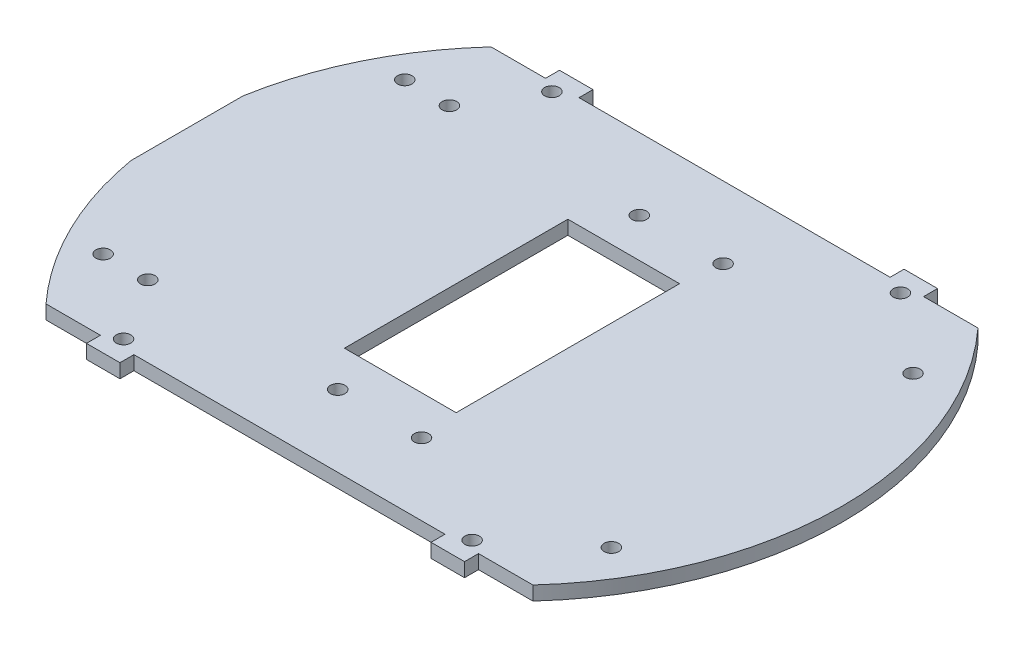
SolidWorks part; units mm, degrees
material "Acrylic (Medium-high impact)"
ref_plane "Front Plane" through (0, 0, 0) normal (0, 0, 1) x (1, 0, 0)
ref_plane "Top Plane" through (0, 0, 0) normal (0, 1, 0) x (1, 0, 0)
ref_plane "Right Plane" through (0, 0, 0) normal (1, 0, 0) x (0, 0, -1)
sketch "Sketch1" plane through (0, 0, 0) normal (0, 1, 0) x (1, 0, 0)
  line L0 (-73.9169, 12.7) -> (-73.9169, -12.7)
  line L1 (-35.3642, -50.6035) -> (-35.3642, -53.7785)
  line L2 (-55.356, -50.6035) -> (-42.9842, -50.6035)
  line L3 (-55.356, 50.6035) -> (-42.9842, 50.6035)
  line L4 (-48.5169, -34.29) -> (-48.5169, 34.29) construction
  line L5 (-48.5169, 34.29) -> (-5.3369, 34.29) construction
  line L6 (-5.3369, 34.29) -> (-5.3369, -34.29) construction
  line L7 (-5.3369, -34.29) -> (-48.5169, -34.29) construction
  line L8 (-73.9169, 0) -> (-48.5169, 0) construction
  line L9 (0, 50.6035) -> (0, -51.6195) construction
  line L10 (-73.9169, 12.7) -> (-73.9169, -12.7) construction
  line L11 (-12.7, 25.4) -> (12.7, 25.4)
  line L12 (-12.7, 25.4) -> (-12.7, -25.4)
  line L13 (-12.7, -25.4) -> (12.7, -25.4)
  line L14 (12.7, 25.4) -> (12.7, -25.4)
  line L15 (0, 0) -> (0, 25.4) construction
  line L16 (0, 0) -> (-12.7, 0) construction
  line L17 (13.7131, 34.29) -> (13.7131, -34.29) construction
  line L18 (13.7131, -34.29) -> (56.8931, -34.29) construction
  line L19 (56.8931, -34.29) -> (56.8931, 34.29) construction
  line L20 (56.8931, 34.29) -> (13.7131, 34.29) construction
  line L21 (39.6269, 48.6985) -> (39.6269, 50.6035) construction
  line L22 (39.6269, -48.6985) -> (39.6269, -50.6035) construction
  line L23 (-39.6269, -48.6985) -> (-39.6269, -50.6035) construction
  line L24 (-39.6269, 48.6985) -> (-39.6269, 50.6035) construction
  line L25 (39.6269, 48.6985) -> (41.2779, 48.6985) construction
  line L26 (39.6269, -48.6985) -> (41.2779, -48.6985) construction
  line L27 (-35.3642, -50.6035) -> (35.3642, -50.6035)
  line L28 (35.3642, -50.6035) -> (35.3642, -53.7785)
  line L29 (35.3642, -53.7785) -> (42.9842, -53.7785)
  line L30 (42.9842, -50.6035) -> (42.9842, -53.7785)
  line L31 (-35.3642, -53.7785) -> (-42.9842, -53.7785)
  line L32 (-42.9842, -50.6035) -> (-42.9842, -53.7785)
  line L33 (42.9842, 50.6035) -> (42.9842, 53.7785)
  line L34 (35.3642, 53.7785) -> (42.9842, 53.7785)
  line L35 (35.3642, 50.6035) -> (35.3642, 53.7785)
  line L36 (-35.3642, 50.6035) -> (-35.3642, 53.7785)
  line L37 (-35.3642, 53.7785) -> (-42.9842, 53.7785)
  line L38 (-42.9842, 50.6035) -> (-42.9842, 53.7785)
  line L39 (42.9842, -50.6035) -> (55.356, -50.6035)
  line L40 (42.9842, 50.6035) -> (55.356, 50.6035)
  line L41 (-35.3642, 50.6035) -> (35.3642, 50.6035)
  arc A0 (-73.9169, -12.7) -> (-55.356, -50.6035) centre (0, 0) ccw
  circle A1 centre (13.7131, 34.29) radius 1.651
  arc A2 (-55.356, 50.6035) -> (-73.9169, 12.7) centre (0, 0) ccw
  arc A3 (55.356, -50.6035) -> (55.356, 50.6035) centre (0, 0) ccw
  circle A4 centre (-58.6769, -34.29) radius 1.651
  circle A5 centre (-58.6769, 34.29) radius 1.651
  circle A6 centre (-39.6269, 48.6985) radius 1.651
  circle A7 centre (39.6269, 48.6985) radius 1.651
  circle A8 centre (-39.6269, -48.6985) radius 1.651
  circle A9 centre (39.6269, -48.6985) radius 1.651
  circle A10 centre (56.8931, 34.29) radius 1.651
  circle A11 centre (-58.6769, 34.29) radius 1.651 construction
  circle A12 centre (-48.5169, 34.29) radius 1.651
  circle A13 centre (-5.3369, 34.29) radius 1.651
  circle A14 centre (-5.3369, -34.29) radius 1.651
  circle A15 centre (-48.5169, -34.29) radius 1.651
  circle A16 centre (13.7131, -34.29) radius 1.651
  circle A17 centre (56.8931, -34.29) radius 1.651
  point P58 (0, 0)
  dimension "D3" = 3.302
  dimension "D1" = 43.18
  dimension "D2" = 68.58
  dimension "D4" = 25.4
  dimension "D5" = 25.4
  dimension "D6" = 50.8
  dimension "D7" = 19.05
  dimension "D10" = 19.05
extrude "Boss-Extrude1" add sketch "Sketch1" along normal blind 3.175
